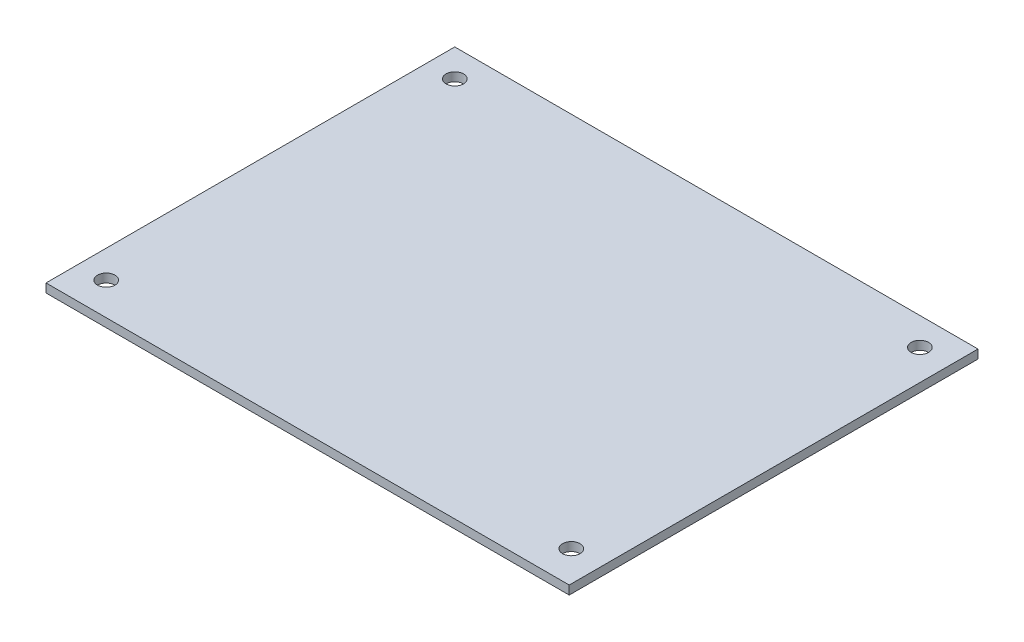
SolidWorks part; units mm, degrees
ref_plane "Front Plane" through (0, 0, 0) normal (0, 0, 1) x (1, 0, 0)
ref_plane "Top Plane" through (0, 0, 0) normal (0, 1, 0) x (1, 0, 0)
ref_plane "Right Plane" through (0, 0, 0) normal (1, 0, 0) x (0, 0, -1)
sketch "Sketch1" plane through (0, 0, 0) normal (0, 1, 0) x (1, 0, 0)
  line L1 (0, 0) -> (96, 0)
  line L2 (0, 0) -> (0, 75)
  line L3 (0, 75) -> (96, 75)
  line L4 (96, 0) -> (96, 75)
  circle A0 centre (5.08, 69.92) radius 1.6
  circle A1 centre (90.412, 69.92) radius 1.6
  circle A2 centre (90.412, 5.969) radius 1.6
  circle A3 centre (5.08, 5.969) radius 1.6
  dimension "D3" = 3.2
  dimension "D1" = 96
  dimension "D2" = 75
  dimension "D4" = 5.08
  dimension "D5" = 5.08
  dimension "D6" = 5.969
  dimension "D7" = 5.588
extrude "Boss-Extrude1" add sketch "Sketch1" along normal blind 1.6
sketch "Sketch2" plane through (0, 1.6, 0) normal (0, 1, 0) x (1, 0, 0)
  line L0 (96, 75) -> (0, 75) construction
  line L1 (96, 0) -> (96, 75) construction
  point P0 (80.252, 69.92)
  point P1 (52.566, 69.92)
  point P2 (39.993, 59.506)
  dimension "D1" = 5.08
  dimension "D2" = 15.748
  dimension "D3" = 27.686
  dimension "D4" = 12.573
  dimension "D5" = 10.414
